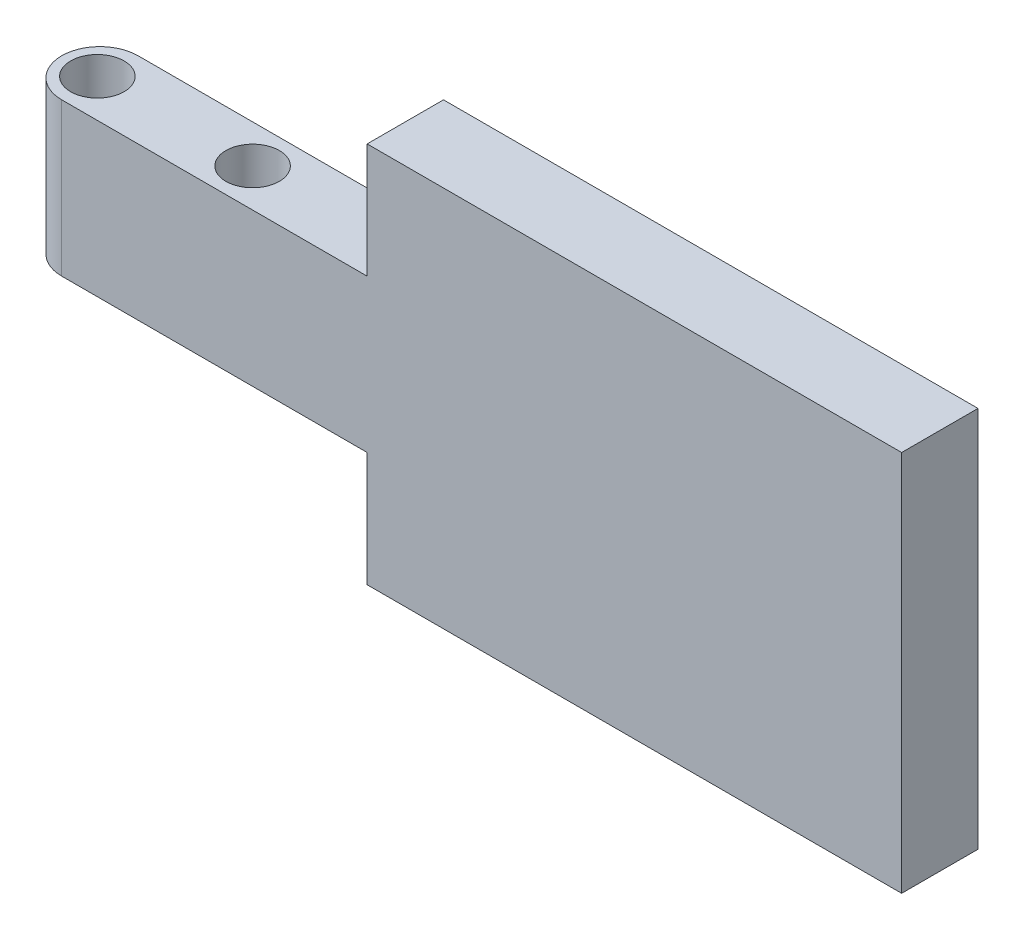
SolidWorks part; units mm, degrees
ref_plane "Front Plane" through (0, 0, 0) normal (0, 0, 1) x (1, 0, 0)
ref_plane "Top Plane" through (0, 0, 0) normal (0, 1, 0) x (1, 0, 0)
ref_plane "Right Plane" through (0, 0, 0) normal (1, 0, 0) x (0, 0, -1)
sketch "Sketch1" plane through (0, 0, 0) normal (0, 1, 0) x (1, 0, 0)
  line L1 (-35, -5) -> (35, -5)
  line L2 (-35, -5) -> (-35, 5)
  line L3 (-35, 5) -> (35, 5)
  line L4 (35, -5) -> (35, 5)
  line L5 (-35, -5) -> (35, 5) construction
  line L6 (-35, 5) -> (35, -5) construction
  point P0 (0, 0)
  dimension "D1" = 10
  dimension "D2" = 70
extrude "Boss-Extrude1" add sketch "Sketch1" along normal blind 25 and the other way blind 25 contours L2 L1 L4 L3
sketch "Sketch2" plane through (0, 0, 0) normal (0, 1, 0) x (1, 0, 0)
  line L0 (-75, 5) -> (-35, 5)
  line L1 (-35, 5) -> (-35, -5)
  line L2 (-35, -5) -> (-75, -5)
  arc A0 (-75, 5) -> (-75, -5) centre (-75, 0) ccw
  point P6 (0, 0)
  point P10 (-75, -5)
  dimension "D1" = 10
  dimension "D2" = 75
extrude "Boss-Extrude2" add sketch "Sketch2" along normal blind 10 and the other way blind 10
sketch "Sketch3" plane through (0, 0, 0) normal (0, 1, 0) x (1, 0, 0)
  circle A0 centre (-75.3332, 0) radius 3.5
  circle A1 centre (-55, 0) radius 3.5
  point P4 (0, 0)
  dimension "D1" = 7
  dimension "D2" = 7
  dimension "D3" = 75.3332
  dimension "D4" = 55
extrude "Cut-Extrude1" cut sketch "Sketch3" against normal blind 16 and the other way blind 19
